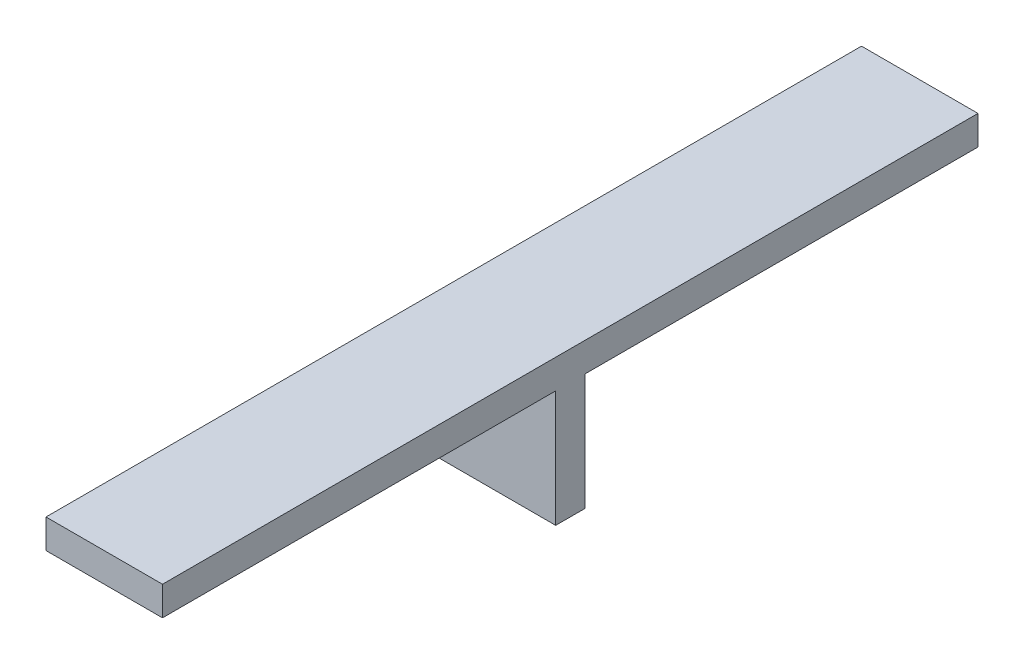
SolidWorks part; units mm, degrees
ref_plane "Front Plane" through (0, 0, 0) normal (0, 0, 1) x (1, 0, 0)
ref_plane "Top Plane" through (0, 0, 0) normal (0, 1, 0) x (1, 0, 0)
ref_plane "Right Plane" through (0, 0, 0) normal (1, 0, 0) x (0, 0, -1)
sketch "Sketch1" plane through (0, 0, 0) normal (0, 1, 0) x (1, 0, 0)
  line L1 (-12.7, -88.9) -> (12.7, -88.9)
  line L2 (-12.7, -88.9) -> (-12.7, 88.9)
  line L3 (-12.7, 88.9) -> (12.7, 88.9)
  line L4 (12.7, -88.9) -> (12.7, 88.9)
  line L5 (-12.7, -88.9) -> (12.7, 88.9) construction
  line L6 (-12.7, 88.9) -> (12.7, -88.9) construction
  point P0 (0, 0)
  dimension "D1" = 177.8
  dimension "D2" = 25.4
extrude "Boss-Extrude1" add sketch "Sketch1" along normal blind 6.35
sketch "Sketch2" plane through (0, 0, 0) normal (0, -1, 0) x (-1, 0, 0)
  line L0 (-12.7, -88.9) -> (-12.7, 88.9) construction
  line L1 (12.7, 3.175) -> (-12.7, 3.175)
  line L2 (12.7, 3.175) -> (12.7, -3.175)
  line L3 (12.7, -3.175) -> (-12.7, -3.175)
  line L4 (-12.7, 3.175) -> (-12.7, -3.175)
  line L5 (12.7, 3.175) -> (-12.7, -3.175) construction
  line L6 (12.7, -3.175) -> (-12.7, 3.175) construction
  point P0 (0, 0)
  dimension "D1" = 6.35
extrude "Boss-Extrude2" add sketch "Sketch2" along normal blind 25.4
